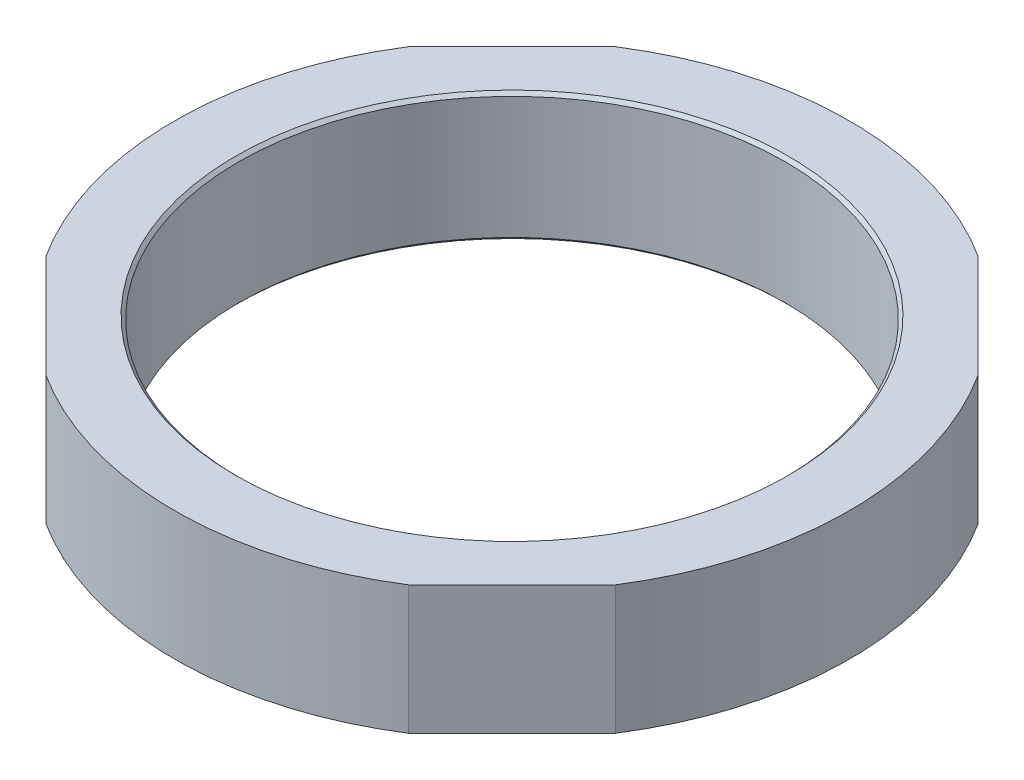
SolidWorks part; units mm, degrees
material "Ceramic Porcelain"
ref_plane "Front Plane" through (0, 0, 0) normal (0, 0, 1) x (1, 0, 0)
ref_plane "Top Plane" through (0, 0, 0) normal (0, 1, 0) x (1, 0, 0)
ref_plane "Right Plane" through (0, 0, 0) normal (1, 0, 0) x (0, 0, -1)
ref_axis "CentralAxis" through (0, 1.1, 0) along (0, -1, 0)
sketch "BaseS" plane through (0, 0, 0) normal (0, 1, 0) x (1, 0, 0)
  circle A0 centre (0, 0) radius 17
  circle A1 centre (0, 0) radius 21
  dimension "InnerDiameter" = 34
  dimension "OuterDiameter" = 42
extrude "Base" add sketch "BaseS" along normal mid plane 8
sketch "FlatCutS" plane through (0, 0, 0) normal (0, 1, 0) x (1, 0, 0)
  line L0 (11.2747, 17.7167) -> (17.7167, 11.2747)
  line L1 (0, 0) -> (14.4957, 14.4957) construction
  line L2 (0, 0) -> (21, 0) construction
  line L3 (0, 0) -> (-14.8492, 14.8492) construction
  line L4 (14.4957, 14.4957) -> (14.8492, 14.8492) construction
  circle A0 centre (0, 0) radius 21 construction
  arc A1 (17.7167, 11.2747) -> (11.2747, 17.7167) centre (0, 0) ccw
  dimension "Angle" = 45
  dimension "RefCutWidth" = 41
  dimension "CutWidth" = 0.5
extrude "FlatCut" cut sketch "FlatCutS" against normal through all both and the other way through all
pattern_circular "FCCirPattern" count 4 over 360 about axis through (0, 1.1, 0) along (0, -1, 0) of "FlatCut"
chamfer "BaseChamfer" distance 0.2 angle 45 2 edges at (0, 4, 17) (0, -4, 17)
